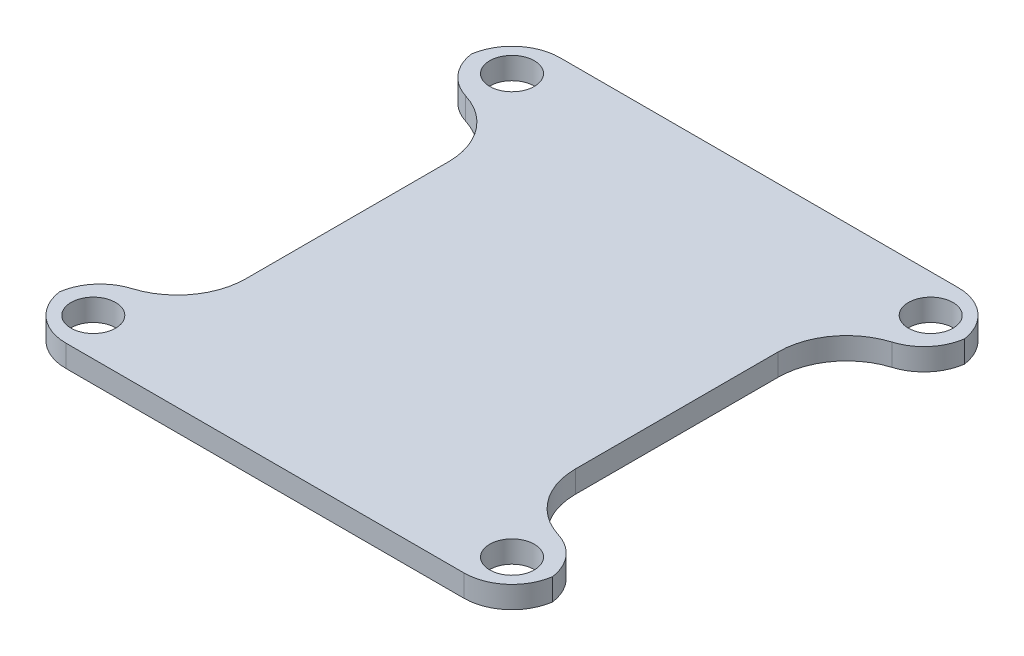
SolidWorks part; units mm, degrees
ref_plane "Front Plane" through (0, 0, 0) normal (0, 0, 1) x (1, 0, 0)
ref_plane "Top Plane" through (0, 0, 0) normal (0, 1, 0) x (1, 0, 0)
ref_plane "Right Plane" through (0, 0, 0) normal (1, 0, 0) x (0, 0, -1)
sketch "Sketch1" plane through (0, 0, 0) normal (0, 1, 0) x (1, 0, 0)
  line L0 (0, 18) -> (0, -18) construction
  line L1 (-18, 18) -> (18, 18)
  line L2 (-18, 18) -> (-18, -18)
  line L3 (-18, -18) -> (18, -18)
  line L4 (18, 18) -> (18, -18)
  line L5 (-18, 18) -> (18, -18) construction
  line L6 (-18, -18) -> (18, 18) construction
  line L7 (12, 18) -> (-12, 18)
  line L8 (12, 18) -> (12, -18)
  line L9 (12, -18) -> (-12, -18)
  line L10 (-12, 18) -> (-12, -18)
  line L11 (12, 18) -> (-12, -18) construction
  line L12 (12, -18) -> (-12, 18) construction
  line L13 (-18, 0) -> (18, 0) construction
  line L14 (-15.25, 12) -> (-15.25, -12) construction
  line L15 (18, 12) -> (-18, 12)
  line L16 (18, 12) -> (18, -12)
  line L17 (18, -12) -> (-18, -12)
  line L18 (-18, 12) -> (-18, -12)
  line L19 (18, 12) -> (-18, -12) construction
  line L20 (18, -12) -> (-18, 12) construction
  circle A0 centre (-15.25, 15.25) radius 1.625
  circle A1 centre (15.25, 15.25) radius 1.625
  circle A2 centre (15.25, -15.25) radius 1.625
  circle A3 centre (-15.25, -15.25) radius 1.625
  point P0 (0, 0)
  point P5 (0, 0)
  point P23 (0, 0)
  point P28 (0, 0)
  dimension "D4" = 3.25
  dimension "D1" = 36
  dimension "D2" = 36
  dimension "D3" = 24
  dimension "D5" = 30.5
  dimension "D6" = 30.5
extrude "Boss-Extrude1" add sketch "Sketch1" along normal blind 1.6 contours L15 L8 L1 L10 | L17 L8 L15 L10 | L4 L17 L8 L3 A2 | L8 L17 L10 L3 | L10 L17 L2 L3 A3 | L15 L4 L1 L8 A1 | L15 L10 L1 L2 A0 region at (-15, 0, -17.9151) region at (0, 0, -15) region at (15, 0, -17.9151) region at (0, 0, 0) region at (-15, 0, 12.0849) region at (0, 0, 15) region at (15, 0, 12.0849)
fillet "Fillet1" radius 3.5 8 edges at (-18, 0.8, 12) (-18, 0.8, -12) (18, 0.8, -12) (18, 0.8, 12) (18, 0.8, 18) (-18, 0.8, 18) (-18, 0.8, -18) (18, 0.8, -18)
fillet "Fillet2" radius 5 4 edges at (12, 0.8, -12) (12, 0.8, 12) (-12, 0.8, 12) (-12, 0.8, -12)
